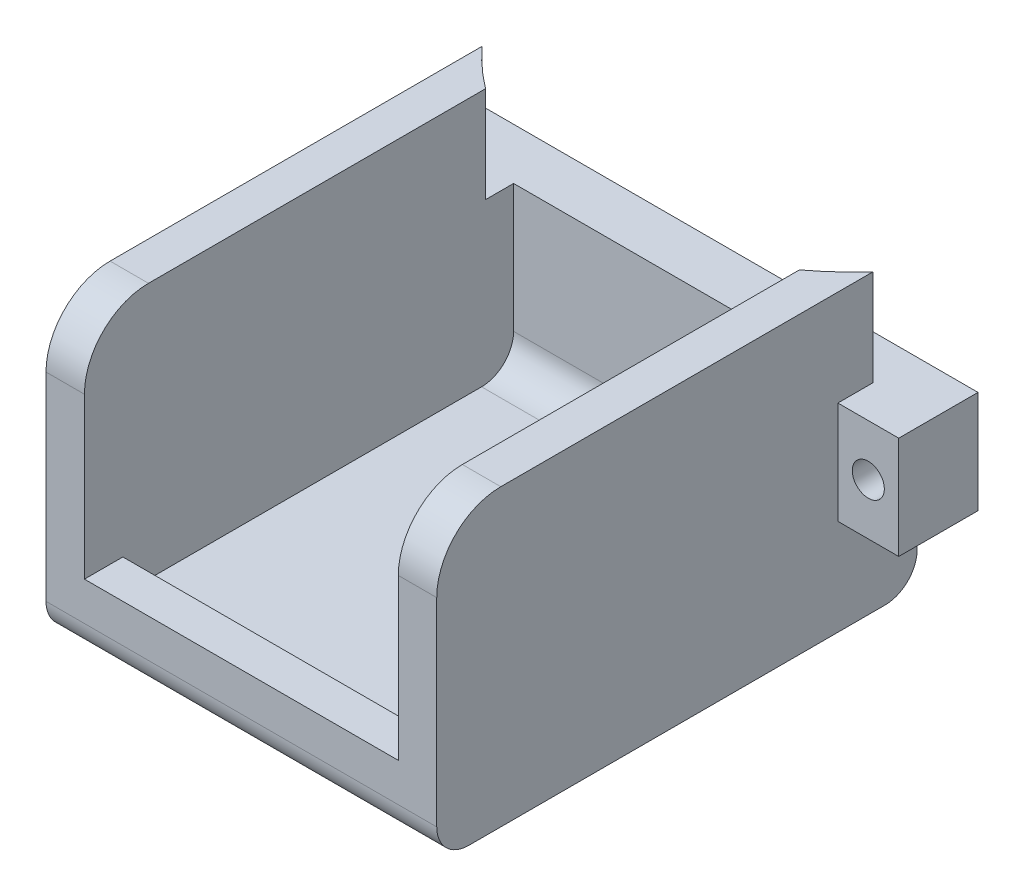
SolidWorks part; units mm, degrees
ref_plane "Front Plane" through (0, 0, 0) normal (0, 0, 1) x (1, 0, 0)
ref_plane "Top Plane" through (0, 0, 0) normal (0, 1, 0) x (1, 0, 0)
ref_plane "Right Plane" through (0, 0, 0) normal (1, 0, 0) x (0, 0, -1)
sketch "Sketch1" plane through (0, 0, 0) normal (0, 1, 0) x (1, 0, 0)
  circle A3 centre (0, 0) radius 40
extrude "Boss-Extrude1" add sketch "Sketch1" along normal blind 16
sketch "Sketch2" plane through (0, 16, 0) normal (0, 1, 0) x (1, 0, 0)
  line L1 (20.5, -20.5) -> (-20.5, -20.5)
  line L2 (20.5, -20.5) -> (20.5, 20.5)
  line L3 (20.5, 20.5) -> (-20.5, 20.5)
  line L4 (-20.5, -20.5) -> (-20.5, 20.5)
  point P4 (0, 0)
  dimension "D1" = 41
  dimension "D2" = 20.5
  dimension "D3" = 20.5
extrude "Cut-Extrude1" cut sketch "Sketch2" against normal through all
ref_plane "Plane1" through (0, 0, 0) normal (-1, 0, 0) x (0, 0, 1)
sketch "Sketch13" plane through (0, 0, 20.5) normal (0, 0, -1) x (-1, 0, 0)
  line L1 (-30.5, 31) -> (30.5, 31)
  line L2 (-30.5, 31) -> (-30.5, -15)
  line L3 (-30.5, -15) -> (30.5, -15)
  line L4 (30.5, 31) -> (30.5, -15)
  line L6 (20.5, 0) -> (20.5, 16) construction
  line L7 (-20.5, 0) -> (-20.5, 16) construction
  line L8 (20.5, 0) -> (-20.5, 0) construction
  line L9 (20.5, 16) -> (-20.5, 16) construction
  dimension "D1" = 10
  dimension "D2" = 10
  dimension "D3" = 15
  dimension "D4" = 15
extrude "Boss-Extrude4" add sketch "Sketch13" against normal blind 75
sketch "Sketch14" plane through (0, 31, 0) normal (0, 1, 0) x (1, 0, 0)
  line L0 (-30.5, -95.5) -> (30.5, -95.5) construction
  line L1 (24.5, -95.5) -> (-24.5, -95.5)
  line L2 (24.5, -95.5) -> (24.5, -28.5)
  line L3 (24.5, -28.5) -> (-24.5, -28.5)
  line L4 (-24.5, -95.5) -> (-24.5, -28.5)
  line L5 (30.5, -95.5) -> (30.5, -20.5) construction
  line L6 (-30.5, -95.5) -> (-30.5, -20.5) construction
  line L7 (-30.5, -20.5) -> (30.5, -20.5) construction
  dimension "D1" = 6
  dimension "D2" = 6
  dimension "D3" = 8
extrude "Cut-Extrude2" cut sketch "Sketch14" against normal blind 35
sketch "Sketch15" plane through (0, -4, 0) normal (0, 1, 0) x (1, 0, 0)
  line L0 (24.5, -95.5) -> (24.5, -28.5) construction
  line L1 (-24.5, -28.5) -> (24.5, -28.5)
  line L2 (-24.5, -28.5) -> (-24.5, -89.5)
  line L3 (-24.5, -89.5) -> (24.5, -89.5)
  line L4 (24.5, -28.5) -> (24.5, -89.5)
  line L5 (-24.5, -95.5) -> (24.5, -95.5) construction
  dimension "D1" = 6
extrude "Cut-Extrude3" cut sketch "Sketch15" against normal blind 5
fillet "Fillet1" radius 10 2 edges at (27.5, 31, 95.5) (-27.5, 31, 95.5)
fillet "Fillet2" radius 5 4 edges at (0, -9, 89.5) (0, -15, 95.5) (0, -15, 20.5) (0, -9, 28.5)
sketch "Sketch17" plane through (0, 16, 0) normal (0, 1, 0) x (1, 0, 0)
  circle A0 centre (0, 0) radius 41
  dimension "D1" = 82
extrude "Cut-Extrude5" cut sketch "Sketch17" along normal up to next
sketch "Sketch18" plane through (0, 16, 0) normal (0, 1, 0) x (1, 0, 0)
  line L0 (-20.5, 20.5) -> (-20.5, -20.5) construction
  line L1 (20.5, -20.5) -> (20.5, 20.5) construction
  line L2 (-20.5, -20.5) -> (20.5, -20.5) construction
  line L3 (-20.5, 20.5) -> (-20.5, -20.5) construction
  line L4 (20.5, -20.5) -> (20.5, 20.5) construction
  line L5 (-20.5, -20.5) -> (20.5, -20.5) construction
  line L6 (40, 0) -> (20.5, 0) construction
  line L8 (20.5, 0) -> (20.5, -20.5)
  line L9 (20.5, -20.5) -> (-20.5, -20.5)
  line L10 (-20.5, 0) -> (-20.5, -20.5)
  line L11 (40, 0) -> (20.5, 0)
  line L12 (40, 0) -> (40, -32.8748)
  line L13 (40, -32.8748) -> (24.5, -32.8748)
  line L14 (-40, 0) -> (-40, -32.8748)
  line L15 (24.5, -32.8748) -> (24.5, -28.5) construction
  line L16 (24.5, -28.5) -> (-24.5, -28.5) construction
  line L17 (-24.5, -28.5) -> (-24.5, -32.8748) construction
  line L18 (-24.5, -28.5) -> (-24.5, -32.8748)
  line L19 (24.5, -28.5) -> (-24.5, -28.5)
  line L20 (24.5, -32.8748) -> (24.5, -28.5)
  line L21 (-20.5, 0) -> (-40, 0)
  line L22 (-20.5, 0) -> (-40, 0) construction
  line L23 (-24.5, -32.8748) -> (-40, -32.8748)
  arc A0 (30.5, -25.8795) -> (-30.5, -25.8795) centre (0, 0) ccw construction
extrude "Boss-Extrude5" add sketch "Sketch18" against normal up to surface (16 mm away) up to face at (0, 0, 3.3599)
sketch "Sketch16" plane through (20.5, 0, 0) normal (-1, 0, 0) x (0, 0, 1)
  line L0 (20.5, 16) -> (-20.5, 16) construction
  line L2 (-20.5, 0) -> (-20.5, 16) construction
  circle A0 centre (0, 8) radius 3
  dimension "D1" = 6
  dimension "D2" = 8
  dimension "D3" = 20.5
extrude "Cut-Extrude4" cut sketch "Sketch16" against normal through all and the other way through all
sketch "Sketch19" plane through (0, 0, 32.8748) normal (0, 0, 1) x (1, 0, 0)
  line L0 (-40, 0) -> (-40, 16) construction
  line L1 (-40, 16) -> (-30.5, 16) construction
  line L2 (30.5, 16) -> (40, 16) construction
  line L3 (40, 0) -> (40, 16) construction
  point P0 (-35.25, 8)
  point P1 (35.25, 8)
  dimension "D1" = 4.75
  dimension "D2" = 8
  dimension "D3" = 8
  dimension "D4" = 4.75
hole_wizard "Ø5.0mm Dowel Hole1" positions "3DSketch1" profile "Sketch20" hole size "Ø5.0" standard "ANSI Metric"
sketch3d "3DSketch1"
  point P0 (-35.25, 8, 32.8748)
  point P3 (35.25, 8, 32.8748)
sketch "Sketch20" plane through (-35.25, 8, 32.8748) normal (1, 0, 0) x (0, -1, 0)
  line L0 (0, 0) -> (0, 26.5022)
  line L1 (0, 26.5022) -> (2.5, 25)
  line L2 (2.5, 25) -> (2.5, 0)
  line L5 (2.5, 0) -> (0, 0)
  line L10 (0, 26.5022) -> (-2.5, 25) construction
  line L11 (0, -6.35) -> (0, 107.95) construction
  dimension "Hole Dia." = 5
  dimension "Hole Depth" = 25
  dimension "Drill Angle" = 118
sketch "Sketch22" plane through (0, 16, -16) normal (0, -1, 0) x (1, 0, 0)
  line L1 (-24.5, 111.5) -> (24.5, 111.5) construction
  line L3 (-40, 16) -> (-40, 48.8748) construction
  line L5 (40, 48.8748) -> (40, 16) construction
  line L7 (-20.5, 36.5) -> (20.5, 36.5) construction
  line L8 (-24.5, 111.5) -> (24.5, 111.5) construction
  line L13 (-40, 16) -> (-40, 48.8748) construction
  line L14 (40, 48.8748) -> (40, 16) construction
  line L15 (-20.5, 36.5) -> (20.5, 36.5) construction
  line L17 (40, 36.5) -> (-40, 36.5)
  line L18 (40, 36.5) -> (40, 111.5)
  line L19 (40, 111.5) -> (-40, 111.5)
  line L20 (-40, 36.5) -> (-40, 111.5)
  line L21 (40, 36.5) -> (-40, 36.5)
  line L22 (40, 36.5) -> (40, -24)
  line L23 (40, -24) -> (-40, -24)
  line L24 (-40, 36.5) -> (-40, -24)
  arc A0 (-40, 16) -> (40, 16) centre (0, 16) ccw construction
  arc A1 (-40, 16) -> (40, 16) centre (0, 16) ccw construction
  point P16 (0, -24)
  line M37 (40, 48.8748) -> (40, 16)
  arc M38 (40, 16) -> (-40, 16) centre (0, 16) cw
  line M39 (-40, 16) -> (-40, 48.8748)
  line M41 (-20.5, -4.5) -> (20.5, -4.5)
  line M42 (20.5, -4.5) -> (20.5, 36.5)
  line M43 (20.5, 36.5) -> (-20.5, 36.5)
  line M44 (-20.5, 36.5) -> (-20.5, -4.5)
extrude "Cut-Extrude7" cut sketch "Sketch22" against normal through all and the other way through all contours M41 M44 M43 M42 | L17 M37 M38 M39 M44 M41 M42 | L22 L23 M38 | L24 L23 M38 region at (38.997, 16, 10.25) region at (0, 16, 0) region at (31.0653, 16, -31.0653) region at (-31.0653, 16, -31.0653)
